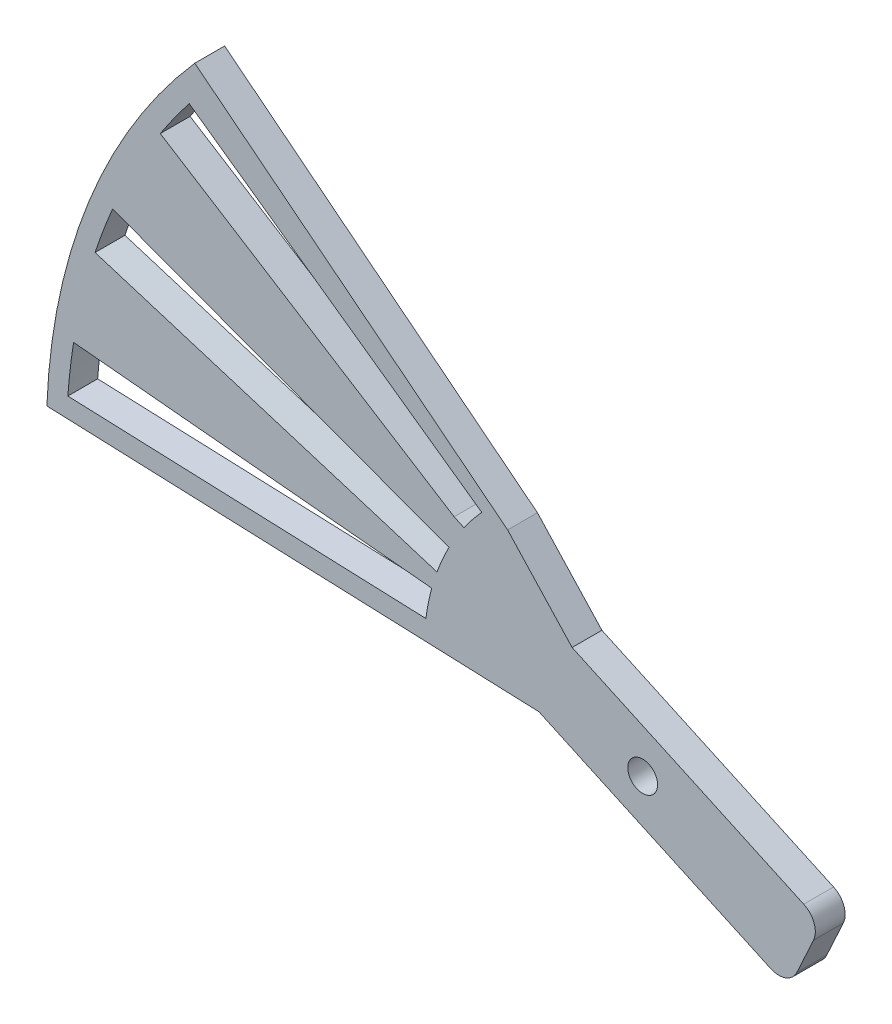
SolidWorks part; units mm, degrees
ref_plane "Front Plane" through (0, 0, 0) normal (0, 0, 1) x (1, 0, 0)
ref_plane "Top Plane" through (0, 0, 0) normal (0, 1, 0) x (1, 0, 0)
ref_plane "Right Plane" through (0, 0, 0) normal (1, 0, 0) x (0, 0, -1)
sketch "Sketch1" plane through (0, 0, 0) normal (0, 0, 1) x (1, 0, 0)
  line L0 (-19.9854, 0.7628) -> (-59.9563, 2.2884)
  line L1 (-16.3569, 14.7123) -> (-16.1915, 14.8941)
  line L2 (0, 0) -> (-50.7795, 31.96) construction
  line L3 (0, 0) -> (-57.3211, 17.7283) construction
  line L4 (-21.8167, 2.8342) -> (-57.8471, 4.2094)
  line L5 (-13.5925, 14.6712) -> (-45.0737, 39.6026)
  line L6 (-21.2283, 5.7759) -> (-57.2696, 9.1759)
  line L7 (-57.0177, 18.6812) -> (-57.0256, 18.6836)
  line L8 (-20.7005, 7.449) -> (-55.1067, 18.0901)
  line L9 (-19.4947, 10.196) -> (-53.3439, 22.7691)
  line L10 (-18.0672, 12.5529) -> (-48.5469, 31.7364)
  line L11 (-50.2398, 32.8019) -> (-50.2468, 32.8063)
  line L12 (0.5327, 0.8463) -> (-50.2468, 32.8063) construction
  line L13 (-16.1915, 14.8941) -> (-45.6332, 35.7997)
  line L15 (-16.3569, 14.7123) -> (-40.8618, 41.162) construction
  line L16 (-13.5925, 14.6712) -> (-40.7774, 44.0137) construction
  line L18 (-54.5167, 25.0585) -> (22.4523, -10.3202) construction
  line L19 (14.6844, -11.152) -> (18.0256, -3.8831)
  line L20 (-7.1038, 7.6676) -> (-13.5925, 14.6712)
  line L21 (-18.9747, 13.124) -> (-16.1345, 11.8185)
  line L22 (-7.1038, 7.6676) -> (18.0256, -3.8831)
  line L23 (-10.4449, 0.3987) -> (-19.9854, 0.7628)
  line L24 (-10.4449, 0.3987) -> (14.6844, -11.152)
  line L25 (-22.3798, 5.8845) -> (-19.4756, 4.5496)
  arc A0 (-45.0737, 39.6026) -> (-59.9563, 2.2884) centre (0, 0) ccw
  arc A1 (-13.5925, 14.6712) -> (-19.9854, 0.7628) centre (0, 0) ccw
  arc A2 (-45.6332, 35.7997) -> (-48.5469, 31.7364) centre (0, 0) ccw
  arc A3 (-16.3569, 14.7123) -> (-18.0672, 12.5529) centre (0, 0) ccw
  arc A4 (-53.3439, 22.7691) -> (-55.1067, 18.0901) centre (0, 0) ccw
  arc A5 (-40.8618, 41.162) -> (-57.8471, 4.2094) centre (0, 0) ccw construction
  arc A6 (-19.4947, 10.196) -> (-20.7005, 7.449) centre (0, 0) ccw
  arc A7 (-21.2283, 5.7759) -> (-21.8167, 2.8342) centre (0, 0) ccw
  arc A8 (-16.3569, 14.7123) -> (-21.8167, 2.8342) centre (0, 0) ccw construction
  arc A9 (-57.2696, 9.1759) -> (-57.8471, 4.2094) centre (0, 0) ccw
  circle A10 centre (0, 0) radius 1.5
  arc A11 (-40.7774, 44.0137) -> (-59.9563, 2.2884) centre (0, 0) ccw construction
  point P16 (0.2955, 0.9554)
  point P33 (-56.1873, 21.4241)
  point P34 (20.7818, -13.9546)
  point P35 (-52.8461, 28.693)
  point P36 (24.1229, -6.6857)
  dimension "D1" = 120
  dimension "D2" = 40
  dimension "D16" = 3
  dimension "D3" = 0.2459
  dimension "D4" = 15
  dimension "D5" = 2
  dimension "15" = 15
  dimension "D6" = 3
  dimension "D7" = 5
  dimension "D8" = 3
  dimension "D9" = 5
  dimension "D11" = 3
  dimension "D12" = 5
  dimension "D13" = 3
  dimension "D15" = 18
  dimension "D10" = 1
extrude "Boss-Extrude2" add sketch "Sketch1" along normal blind 3 contours L0 A0 L5 A1
extrude "Cut-Extrude1" cut sketch "Sketch1<5>" along normal through all contours A6 L9 A4 L8 | L6 A9 L4 A7 | A3 L1 L13 A2 L10 | L4 A9 L6 A7 | L8 A4 L9 A6 region at (-41.1268, 5.6046, 0) region at (-33.401, 24.6128, 0) region at (-38.6238, 15.1254, 0)
sketch "Sketch1<5>" plane through (0, 0, 0) normal (0, 0, 1) x (1, 0, 0) same geometry as "Sketch1"
extrude "Boss-Extrude5" add sketch "Sketch1<8>" along normal blind 3 contours L20 A1 L23 L24 L19 L22 A10 region at (-2.3746, 1.0915, 0)
sketch "Sketch1<8>" plane through (0, 0, 0) normal (0, 0, 1) x (1, 0, 0) same geometry as "Sketch1"
fillet "Fillet1" radius 2 2 edges at (18.0256, -3.8831, 1.5) (14.6844, -11.152, 1.5)
